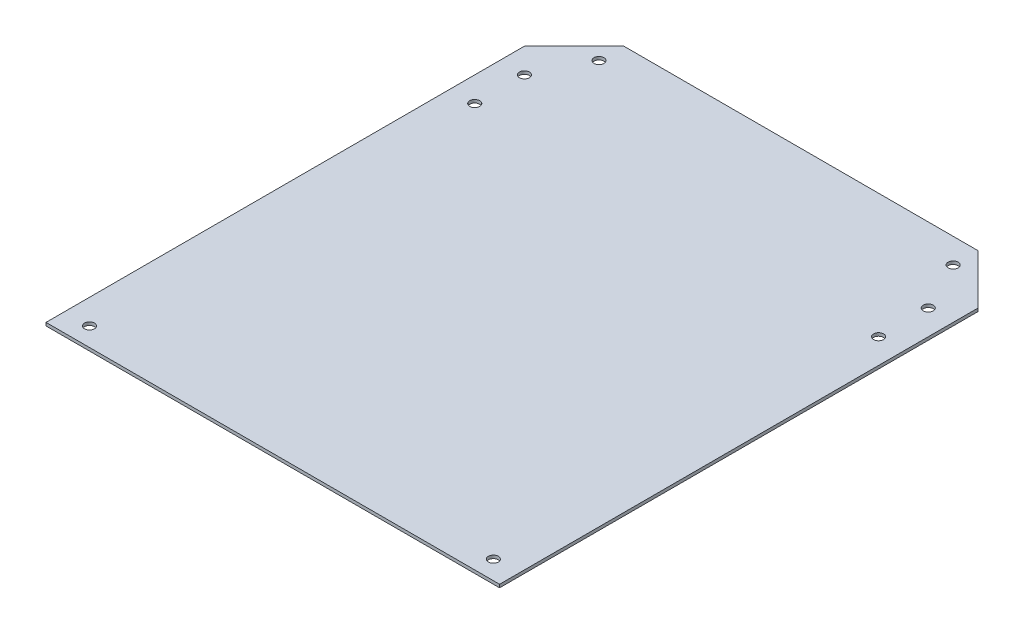
SolidWorks part; units mm, degrees
ref_plane "Front Plane" through (0, 0, 0) normal (0, 0, 1) x (1, 0, 0)
ref_plane "Top Plane" through (0, 0, 0) normal (0, 1, 0) x (1, 0, 0)
ref_plane "Right Plane" through (0, 0, 0) normal (1, 0, 0) x (0, 0, -1)
sketch "Sketch3" plane through (0, 0, 0) normal (0, 1, 0) x (1, 0, 0)
  line L2 (-96.1565, -3.6215) -> (-96.1565, 240.8535)
  line L6 (135.6185, -3.6215) -> (135.6185, 240.8535)
  line L7 (110.2185, 266.2535) -> (-70.7565, 266.2535)
  line L12 (-96.1565, 240.8535) -> (-70.7565, 266.2535)
  line L13 (135.6185, 240.8535) -> (110.2185, 266.2535)
  line L16 (-96.1565, -3.6215) -> (135.6185, -3.6215)
extrude "Boss-Extrude1" add sketch "Sketch3" along normal blind 1.5875
hole_wizard "#10 Clearance Hole1" positions "Sketch11" profile "Sketch12" hole size "#10" standard "ANSI Inch" end condition through all
sketch "Sketch11" plane through (0, 1.5875, 0) normal (0, 1, 0) x (1, 0, 0)
  point P0 (-83.4565, -25.8465)
  point P3 (-83.4565, 202.7535)
  point P6 (-83.4565, 228.1535)
  point P9 (-70.7565, 253.5535)
  point P12 (122.9185, 202.7535)
  point P15 (122.9185, 228.1535)
  point P18 (110.2185, 253.5535)
  point P21 (-83.4565, 5.9035)
  point P24 (122.9185, 5.9035)
sketch "Sketch12" plane through (-83.4565, 1.5875, 25.8465) normal (1, 0, 0) x (0, 0, 1)
  line L0 (0, 0) -> (0, 1.5875)
  line L1 (0, 1.5875) -> (2.5527, 1.5875)
  line L2 (2.5527, 1.5875) -> (2.5527, 0)
  line L5 (2.5527, 0) -> (0, 0)
  line L11 (0, -6.35) -> (0, 107.95) construction
  dimension "Thru Hole Dia." = 5.1054
  dimension "Thru Hole Depth" = 1.5875
